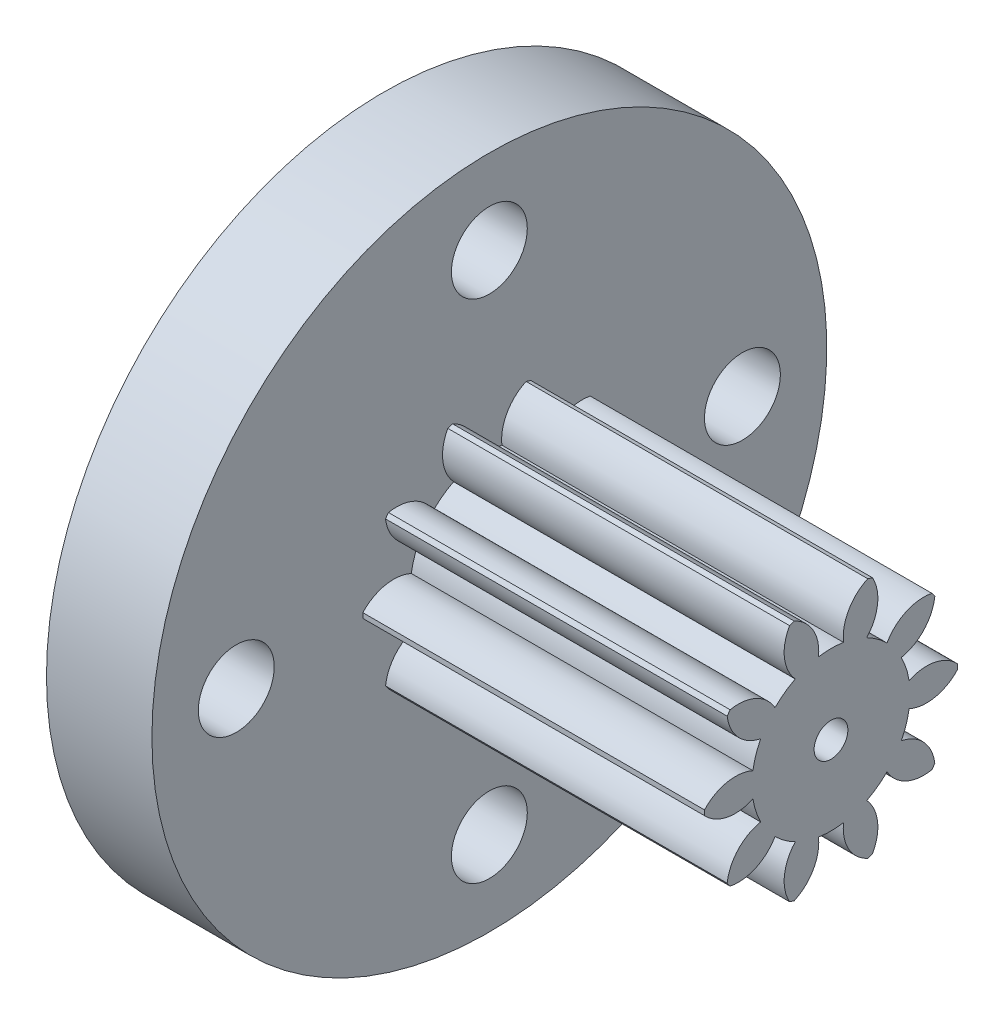
SolidWorks part; units mm, degrees
ref_plane "Plane1" through (0, 0, 0) normal (0, 0, 1) x (1, 0, 0)
ref_plane "Plane2" through (0, 0, 0) normal (0, 1, 0) x (1, 0, 0)
ref_plane "Plane3" through (0, 0, 0) normal (1, 0, 0) x (0, 0, -1)
sketch "HoldingSke" plane through (0, 0, 0) normal (0, 1, 0) x (1, 0, 0)
  line L0 (0, 0) -> (1.9696, -0.3473)
  line L1 (-15, 0) -> (100, 0) construction
  line L2 (0, 0) -> (-2.1039, 2.3779)
  line L3 (0, 0) -> (-11.863, 4.5341)
  line L4 (0, 0) -> (8.5048, 1.4996)
  line L5 (0, 0) -> (-46.8476, -17.4728)
  line L6 (0, 0) -> (-6.6317, -4.4744)
  line L7 (-2.1039, 2.3779) -> (8.6586, 51.2059)
  line L8 (-76.2, 54.61) -> (-76.1, 54.61)
  line L9 (-71.009, 38.7566) -> (-53.1078, 45.2721)
  line L10 (-76.2, 71.12) -> (104.1128, 71.12)
  line L11 (0, 0) -> (-8, 0)
  line L12 (-76.2, 101.6) -> (-76.181, 101.6)
  line L13 (24.9733, 27.94) -> (52.9518, 28.4284)
  line L14 (24.9733, 27.94) -> (24.9743, 27.94)
  line L15 (24.9733, 27.94) -> (100.4006, 29.5858)
  line L16 (-63.627, -0.5) -> (-12.827, -0.5)
  circle A0 centre (0, 0) radius 0.4
  circle A1 centre (0, 0) radius 1.874
  circle A2 centre (0, 0) radius 37.5
  circle A3 centre (0, 0) radius 0.4
  dimension "Num_teeth" = 10
  dimension "Pitch_radius" = 180.3128
  dimension "Width" = 8
sketch "BasProSke" plane through (0, 0, 0) normal (0, 1, 0) x (1, 0, 0)
  line L0 (-10, 0) -> (60, 0) construction
  line L1 (0, 0) -> (0, 3)
  line L2 (0, 0) -> (10.6, 0)
  line L3 (10.6, 0) -> (10.6, 3)
  line L4 (10.6, 3) -> (0, 3)
  dimension "Thickness" = 10.6
  dimension "Diameter" = 6
revolve "Base-Revolve" add sketch "BasProSke" angle 360 about L0
sketch "TooCutSke" plane through (0, 0, 0) normal (1, 0, 0) x (0, 0, -1)
  line L1 (0, 0) -> (0, 107) construction
  line L2 (0, 0) -> (-0.4243, 2.4637) construction
  line L3 (0, 0) -> (-1.5292, 4.7063) construction
  line L4 (-0.4243, 2.4637) -> (-0.7646, 2.3532) construction
  arc A0 (0.2964, 1.8504) -> (-0.2964, 1.8504) centre (0, 0) ccw
  arc A1 (0.9059, 2.8866) -> (-0.9059, 2.8866) centre (0, 0) ccw
  circle A2 centre (0, 0) radius 2.5 construction
  circle A3 centre (0, 0) radius 2.3492 construction
  arc A4 (-0.2964, 1.8504) -> (-0.9059, 2.8866) centre (-1.2901, 1.9633) ccw
  arc A5 (0.9059, 2.8866) -> (0.2964, 1.8504) centre (1.2901, 1.9633) ccw
extrude "ToothCut" cut sketch "TooCutSke" along normal through all
fillet "Breaks" [suppressed] radius 0.01 tangent propagation no
fillet "RootFillets" [suppressed] radius 0.126
pattern_circular "TeethCuts" count 10 over 360 about axis through (-10, 0, 0) along (1, 0, 0) of "ToothCut", "RootFillets", "Breaks"
sketch "HubNeaOneSke" plane through (0, 0, 0) normal (-1, 0, 0) x (0, 0, 1)
  circle A0 centre (0, 0) radius 1.874
  dimension "Diameter" = 3.748
extrude "HubNearOne" [suppressed] add sketch "HubNeaOneSke" along normal blind 39.4001
sketch "HubNeaBotSke" plane through (0, 0, 0) normal (-1, 0, 0) x (0, 0, 1)
  circle A0 centre (0, 0) radius 1.874
  dimension "Diameter" = 3.748
extrude "HubNearBoth" [suppressed] add sketch "HubNeaBotSke" along normal blind 19.7
ref_plane "FarPln" through (10.6, 0, 0) normal (1, 0, 0) x (0, 0, -1)
sketch "HubFarSke" plane through (10.6, 0, 0) normal (1, 0, 0) x (0, 0, -1)
  circle A0 centre (0, 0) radius 1.874
  dimension "Diameter" = 3.748
extrude "HubFar" [suppressed] add sketch "HubFarSke" along normal blind 19.7
sketch "BorSke" plane through (0, 0, 0) normal (1, 0, 0) x (0, 0, -1)
  circle A0 centre (0, 0) radius 0.4
  dimension "Diameter" = 0.8
extrude "Bore" cut sketch "BorSke" along normal mid plane 100.0001
sketch "KeySke" plane through (0, 0, 0) normal (1, 0, 0) x (0, 0, -1)
  line L0 (-0.05, 0) -> (-0.05, 0.5)
  line L1 (-0.05, 0.5) -> (0.05, 0.5)
  line L2 (0.05, 0.5) -> (0.05, 0)
  line L3 (0, 0) -> (0, 34) construction
  line L4 (-0.05, 0) -> (0.05, 0)
  dimension "Width" = 0.1
extrude "Keyway" [suppressed] cut sketch "KeySke" along normal mid plane 100.0001
pattern_circular "Keyway2" [suppressed] count 2 every 90 about axis through (-10, 0, 0) along (1, 0, 0) reverse direction yes
sketch "Sketch1" plane through (0, 0, 0) normal (-1, 0, 0) x (0, 0, 1)
  circle A0 centre (0, 0) radius 8
  dimension "D1" = 16
extrude "Boss-Extrude1" add sketch "Sketch1" against normal blind 2.5
hole_wizard "M1.6 Clearance Hole1" positions "Sketch2" profile "Sketch3" hole size "M1.6" standard "ISO"
sketch "Sketch2" plane through (2.5, 0, 0) normal (1, 0, 0) x (0, 0, -1)
  line L0 (-15.5326, 0) -> (15.8639, 0) construction
  line L2 (0, 11.0318) -> (0, -13.9603) construction
  circle A0 centre (0, 0) radius 6 construction
  point P0 (0, 6)
  point P2 (6, 0)
  point P4 (0, -6)
  point P6 (-6, 0)
  dimension "D1" = 12
sketch "Sketch3" plane through (2.5, 6, 0) normal (0, 1, 0) x (0, 0, -1)
  line L0 (0, 0) -> (0, 4.7908)
  line L1 (0, 4.7908) -> (0.9, 4.25)
  line L2 (0.9, 4.25) -> (0.9, 0)
  line L5 (0.9, 0) -> (0, 0)
  line L10 (0, 4.7908) -> (-0.9, 4.25) construction
  line L11 (0, -6.35) -> (0, 107.95) construction
  dimension "Hole Dia." = 1.8
  dimension "Hole Depth" = 4.25
  dimension "Drill Angle" = 118
equation "' \"Module@HoldingSke\" = 6.35"
equation "' \"Num_teeth@HoldingSke\" = 12"
equation "' \"Ap@HoldingSke\" =  20"
equation "' \"Ap@HoldingSke\" = 20"
equation "' \"Width@HoldingSke\" = 0.5 * 25.4"
equation "' \"Hub_dia@HoldingSke\"= 1 * 25.4"
equation "' \"Hub_dia@HoldingSke\" = 1 * 25.4"
equation "' \"Overall_len@HoldingSke\" = 1.0 * 25.4"
equation "' \"Bore@HoldingSke\" = 0.75 * 25.4"
equation "' \"T_dim@HoldingSke\" = 0.1 * 25.4"
equation "' \"Width@KeySke\" = 0.25 * 25.4"
equation "' \"Show_teeth@HoldingSke\" = 13"
equation "' \"Backlash@HoldingSke\" = 0.009 * 25.4"
equation "' \"Addendum_fac@HoldingSke\" = 1.0"
equation "' \"Dedendum_fac@HoldingSke\" = 1.25"
equation "' \"Dedendum_add@HoldingSke\" = 0.00005 * 25.4"
equation "' \"Clearance_fac@HoldingSke\" = 0.25"
equation "\"Pitch@HoldingSke\" = 1 / \"Module@HoldingSke\""
equation "\"Overcut_dia@TooCutSke\" = (\"Num_teeth@HoldingSke\" + 2 * \"Addendum_fac@HoldingSke\") / \"Pitch@HoldingSke\" + 0.002 * 25.4"
equation "\"Pitch_dia@TooCutSke\" = \"Num_teeth@HoldingSke\" / \"Pitch@HoldingSke\""
equation "\"Base_dia@TooCutSke\" = \"Num_teeth@HoldingSke\" / \"Pitch@HoldingSke\" * cos((\"Ap@HoldingSke\"  * 3.14159265 / 180))"
equation "\"Root_dia@TooCutSke\" = (\"Num_teeth@HoldingSke\" + 2) / \"Pitch@HoldingSke\" - 2 * (\"Addendum_fac@HoldingSke\" + \"Dedendum_fac@HoldingSke\") / \"Pitch@HoldingSke\" - \"Dedendum_add@HoldingSke\" * 2"
equation "\"Half_ang@TooCutSke\" = 180 / \"Num_teeth@HoldingSke\""
equation "\"Half_CT@TooCutSke\" = \"Num_teeth@HoldingSke\" / \"Pitch@HoldingSke\" * sin((3.14159265 / 2 / \"Num_teeth@HoldingSke\")) / 2 - 7 * \"Backlash@HoldingSke\" / 4"
equation "\"Flank_rad@TooCutSke\" = \"Num_teeth@HoldingSke\" / \"Pitch@HoldingSke\" / 5"
equation "\"Radius@RootFillets\" = \"Clearance_fac@HoldingSke\" / \"Pitch@HoldingSke\" + \"Dedendum_add@HoldingSke\""
equation "\"Break_rad@Breaks\" = 0.02 / \"Pitch@HoldingSke\""
equation "\"Thickness@HoldingSke\" = \"Width@HoldingSke\""
equation "\"OAL@HoldingSke\" = \"Thickness@HoldingSke\""
equation "\"MHD@HoldingSke\" = (\"Num_teeth@HoldingSke\" + 2) / \"Pitch@HoldingSke\" - 2 * (\"Addendum_fac@HoldingSke\" + \"Dedendum_fac@HoldingSke\")  / \"Pitch@HoldingSke\" - \"Dedendum_add@HoldingSke\" * 2"
equation "\"MBD@HoldingSke\" = (\"Num_teeth@HoldingSke\" + 2) / \"Pitch@HoldingSke\" - 2 * (\"Addendum_fac@HoldingSke\" + \"Dedendum_fac@HoldingSke\")  / \"Pitch@HoldingSke\" - \"Dedendum_add@HoldingSke\" * 2 - 0.002 * 25.4"
equation "\"MHD@HoldingSke\" = ((sgn( \"MHD@HoldingSke\" - \"Hub_dia@HoldingSke\" )-1)*( \"MHD@HoldingSke\" - \"Hub_dia@HoldingSke\" ))/-2+ \"Hub_dia@HoldingSke\""
equation "\"MBD@HoldingSke\" = ((sgn( \"MBD@HoldingSke\" - \"Bore@HoldingSke\" )-1)*( \"MBD@HoldingSke\" - \"Bore@HoldingSke\" ))/-2+ \"Bore@HoldingSke\""
equation "\"OAL@HoldingSke\" = ((sgn( \"OAL@HoldingSke\" - \"Overall_len@HoldingSke\" )+1)*( \"OAL@HoldingSke\" - \"Overall_len@HoldingSke\" ))/2 + \"Overall_len@HoldingSke\" + 0.000002 * 25.4"
equation "\"Num_teeth@TeethCuts\" = int( \"Show_teeth@HoldingSke\" ) + 1"
equation "\"Num_teeth@TeethCuts\" = ((sgn( \"Num_teeth@TeethCuts\" - \"Num_teeth@HoldingSke\" )-1)*( \"Num_teeth@TeethCuts\" - \"Num_teeth@HoldingSke\" ))/-2+ \"Num_teeth@HoldingSke\""
equation "\"Num_teeth@TeethCuts\" = ((sgn( \"Num_teeth@TeethCuts\" - 2.0)+1)*( \"Num_teeth@TeethCuts\" - 2.0))/2 +2.0"
equation "\"Angle@TeethCuts\" = 360.0 / \"Num_teeth@HoldingSke\""
equation "\"Diameter@BasProSke\" = (\"Num_teeth@HoldingSke\" + 2 * \"Addendum_fac@HoldingSke\") / \"Pitch@HoldingSke\""
equation "\"Thickness@BasProSke\"=10.6"
equation "' \"Fillet_rad@BasProSke\" =  \"Thickness@HoldingSke\" * 0.05"
equation "' \"Fillet_rad@BasProSke\" = \"Thickness@HoldingSke\" * 0.05"
equation "\"MHD@HoldingSke\" = ((sgn( \"MHD@HoldingSke\" - \"Root_dia@TooCutSke\" )-1)*( \"MHD@HoldingSke\" - \"Root_dia@TooCutSke\" ))/-2+ \"Root_dia@TooCutSke\""
equation "\"Diameter@HubNeaOneSke\" = \"MHD@HoldingSke\""
equation "\"Length@HubNearOne\" = \"OAL@HoldingSke\" - \"Thickness@BasProSke\""
equation "\"Diameter@HubNeaBotSke\" = \"MHD@HoldingSke\""
equation "\"Length@HubNearBoth\" = ( \"OAL@HoldingSke\" - \"Thickness@BasProSke\" ) / 2.0"
equation "\"Thickness@FarPln\" = \"Thickness@BasProSke\""
equation "\"Diameter@HubFarSke\" = \"MHD@HoldingSke\""
equation "\"Length@HubFar\" = ( \"OAL@HoldingSke\" - \"Thickness@BasProSke\" ) / 2.0"
equation "\"Diameter@BorSke\" = \"MBD@HoldingSke\""
equation "\"D1@Bore\" = \"OAL@HoldingSke\" * 2.0"
equation "\"D1@Keyway\" = \"OAL@HoldingSke\" * 2.0"
equation "\"Offset@KeySke\" = \"T_dim@HoldingSke\" + \"MBD@HoldingSke\" / 2.0"
